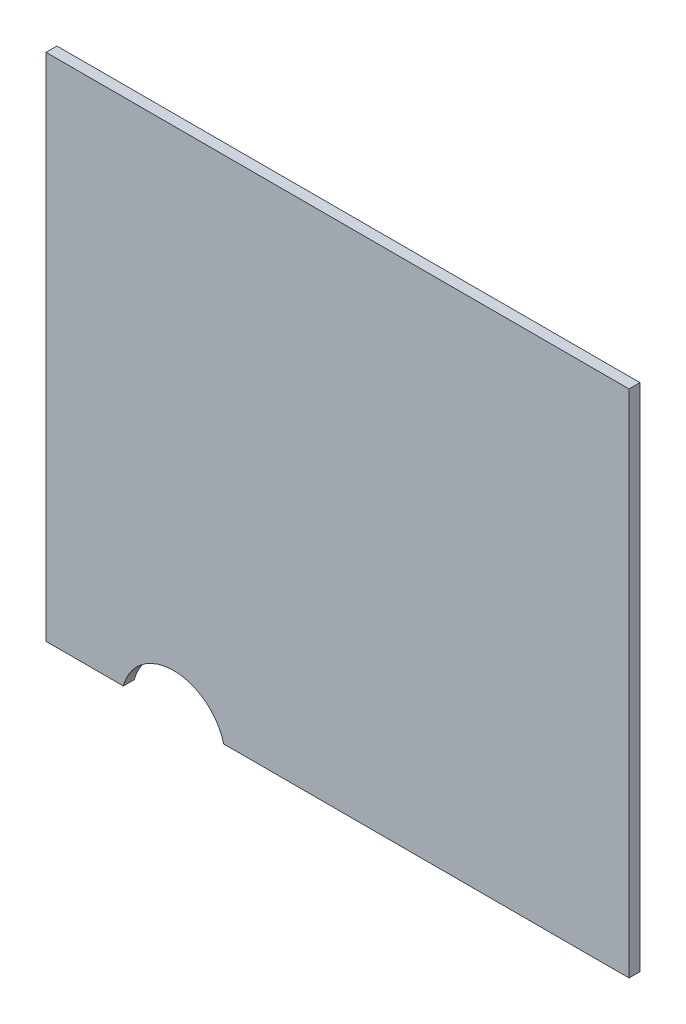
SolidWorks part; units mm, degrees
ref_plane "Front Plane" through (0, 0, 0) normal (0, 0, 1) x (1, 0, 0)
ref_plane "Top Plane" through (0, 0, 0) normal (0, 1, 0) x (1, 0, 0)
ref_plane "Right Plane" through (0, 0, 0) normal (1, 0, 0) x (0, 0, -1)
sketch "Sketch1" plane through (0, 0, 0) normal (0, 0, 1) x (1, 0, 0)
  line L1 (0, 0) -> (160, 0)
  line L2 (0, 0) -> (0, 140)
  line L3 (0, 140) -> (160, 140)
  line L4 (160, 0) -> (160, 140)
  dimension "D1" = 160
  dimension "D2" = 140
extrude "Boss-Extrude1" add sketch "Sketch1" along normal blind 3
sketch "Sketch2" plane through (0, 0, 3) normal (0, 0, 1) x (1, 0, 0)
  line L0 (160, 140) -> (0, 140) construction
  line L2 (0, 140) -> (0, 0) construction
  circle A0 centre (35, -3.69) radius 14.275
  dimension "D1" = 28.55
  dimension "D2" = 35
  dimension "D3" = 143.69
extrude "Cut-Extrude1" cut sketch "Sketch2" against normal blind 3
